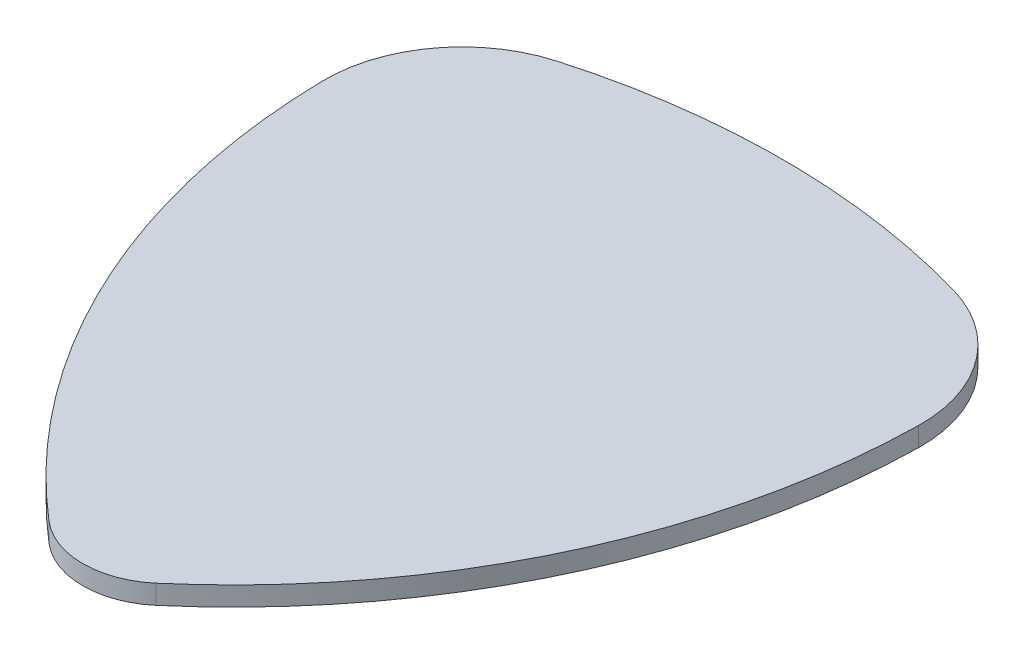
SolidWorks part; units mm, degrees
ref_plane "Front Plane" through (0, 0, 0) normal (0, 0, 1) x (1, 0, 0)
ref_plane "Top Plane" through (0, 0, 0) normal (0, 1, 0) x (1, 0, 0)
ref_plane "Right Plane" through (0, 0, 0) normal (1, 0, 0) x (0, 0, -1)
sketch "Sketch1" plane through (0, 0, 0) normal (0, 1, 0) x (1, 0, 0)
  line L0 (10.6517, -24) -> (10.6517, 4.3553) construction
  arc A0 (0, 0) -> (21.3033, 0) centre (10.6517, -24) cw
  arc A1 (0, 0) -> (10.6517, -24) centre (25.1658, -3.1946) ccw
  arc A2 (21.3033, 0) -> (10.6517, -24) centre (-3.8625, -3.1946) cw
  dimension "D1" = 25.3678
  dimension "D2" = 24
  dimension "D3" = 21.3033
extrude "Boss-Extrude1" add sketch "Sketch1" along normal blind 0.7
fillet "Fillet1" radius 5 1 edges at (21.3033, 0.35, 0)
fillet "Fillet2" radius 5 1 edges at (0, 0.35, 0)
fillet "Fillet3" radius 3 1 edges at (10.6517, 0.35, 24)
scale "Scale1" scale about centroid uniform scaling yes scale factor 1.2
sketch "草图1" plane through (0, 0.77, 0) normal (0, 1, 0) x (1, 0, 0)
  line L0 (10.6517, 4.4668) -> (10.6517, -26.0989) construction
  arc A0 (-2.3677, -2.6268) -> (8.3157, -25.2381) centre (28.0687, -2.0758) ccw construction
  arc A1 (12.9877, -25.2381) -> (23.671, -2.6268) centre (-6.7653, -2.0758) ccw construction
  arc A2 (8.3157, -25.2381) -> (12.9877, -25.2381) centre (10.6517, -22.4989) ccw construction
  arc A3 (19.3233, 3.2501) -> (1.9801, 3.2501) centre (10.6517, -27.0422) ccw construction
  point P8 (10.6517, -26.0989)
  point P12 (10.6517, 4.4668)
